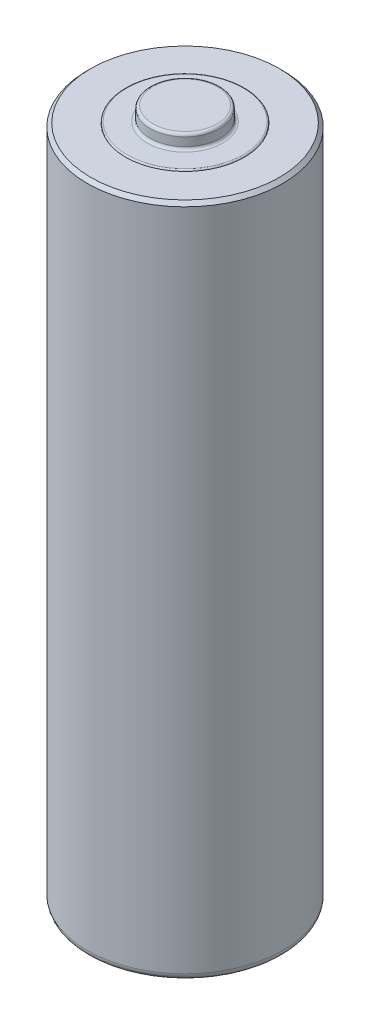
SolidWorks part; units mm, degrees
ref_plane "Front Plane" through (0, 0, 0) normal (0, 0, 1) x (1, 0, 0)
ref_plane "Top Plane" through (0, 0, 0) normal (0, 1, 0) x (1, 0, 0)
ref_plane "Right Plane" through (0, 0, 0) normal (1, 0, 0) x (0, 0, -1)
sketch "Sketch1" plane through (0, 0, 0) normal (0, 1, 0) x (1, 0, 0)
  circle A0 centre (0, 0) radius 7
  dimension "D1" = 14
extrude "Boss-Extrude1" add sketch "Sketch1" along normal blind 24.15 and the other way blind 24.15
fillet "Fillet1" radius 0.5 1 edges at (0, -24.15, 7)
chamfer "Chamfer1" distance 0.25 angle 45 1 edges at (0, 24.15, 7)
sketch "Sketch2" plane through (0, 24.15, 0) normal (0, 1, 0) x (1, 0, 0)
  circle A0 centre (0, 0) radius 4.25
  dimension "D1" = 8.5
extrude "Boss-Extrude2" add sketch "Sketch2" along normal blind 0.1
fillet "Fillet2" radius 0.1 1 edges at (0, 24.25, 4.25)
sketch "Sketch3" plane through (0, 24.25, 0) normal (0, 1, 0) x (1, 0, 0)
  circle A0 centre (0, 0) radius 2.5
  dimension "D1" = 5
extrude "Boss-Extrude3" add sketch "Sketch3" along normal blind 1
fillet "Fillet3" radius 0.2 1 edges at (0, 24.25, 2.5)
fillet "Fillet4" radius 0.2 1 edges at (0, 25.25, 2.5)
